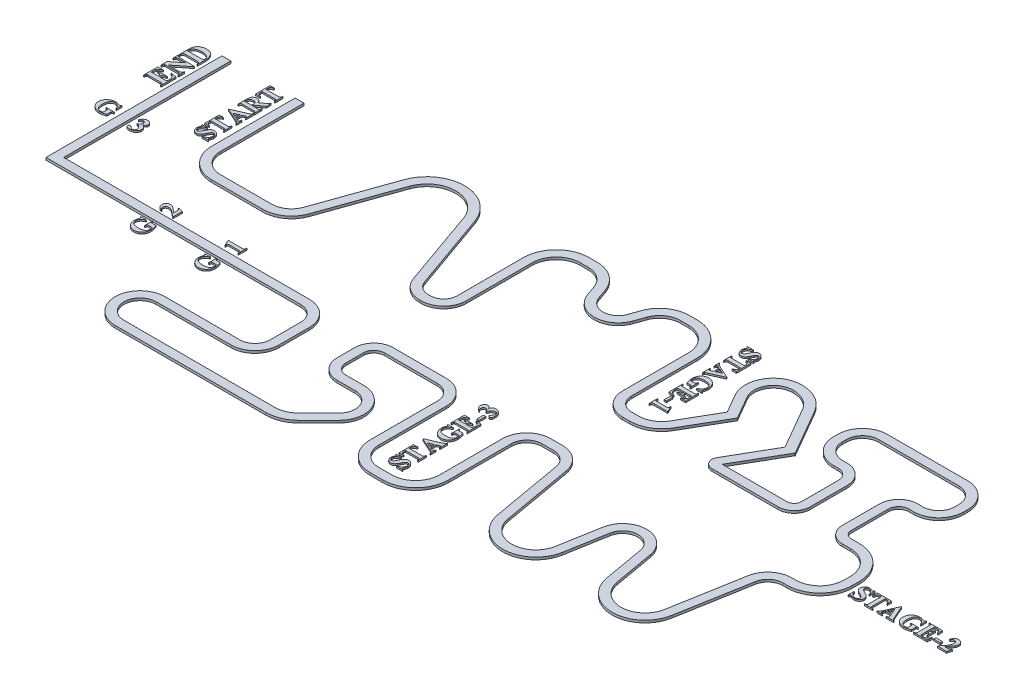
SolidWorks part; units mm, degrees
ref_plane "Front Plane" through (0, 0, 0) normal (0, 0, 1) x (1, 0, 0)
ref_plane "Top Plane" through (0, 0, 0) normal (0, 1, 0) x (1, 0, 0)
ref_plane "Right Plane" through (0, 0, 0) normal (1, 0, 0) x (0, 0, -1)
sketch "Sketch1" plane through (0, 0, 0) normal (0, 1, 0) x (1, 0, 0)
  line L0 (-2000, 850) -> (-2000, 330)
  line L1 (-1820, 150) -> (-1502.2309, 150)
  line L2 (-1332.5468, 269.9393) -> (-1169.6842, 730.0607)
  line L9 (-1000, 1000) -> (-1000, 0) construction
  line L10 (-658.0192, 243.2861) -> (-830.3158, 730.0607)
  line L11 (-52.8541, 763.3772) -> (-30.4035, 699.9494)
  line L14 (-2000, 590) -> (2060.211, 474.7133) construction
  line L30 (1417.787, -380) -> (1417.787, -1000) construction
  line L56 (1565.5082, -503.9528) -> (1609.9593, -756.0472)
  line L58 (1983.3548, -313.9528) -> (1905.4016, -756.0472)
  line L59 (-165.3476, -710.7107) -> (-290.7029, -836.066)
  line L60 (1805.211, 250) -> (1805.211, 480.1871)
  line L62 (-2000, 0) -> (2000, 0) construction
  line L64 (-2000, 1000) -> (2000, 1000) construction
  line L65 (-2000, 1000) -> (-2000, -1000) construction
  line L66 (704.4982, -190) -> (630.3631, -190)
  line L67 (480.3631, -340) -> (480.3631, -730)
  line L68 (330.3631, -880) -> (250.3631, -880)
  line L69 (130.3631, -760) -> (130.3631, -340)
  line L70 (-19.6369, -190) -> (-349.6369, -190)
  line L71 (-469.6369, -310) -> (-469.6369, -420)
  line L72 (-349.6369, -540) -> (-236.0583, -540)
  line L74 (-396.7689, -880) -> (-1334.6369, -880)
  line L75 (-1334.6369, -880) -> (-1334.6369, -680) construction
  line L76 (-1334.6369, -680) -> (-869.6369, -680)
  line L77 (-719.6369, -530) -> (-719.6369, -340)
  line L78 (-869.6369, -190) -> (-2400, -190)
  line L79 (-2000, -1000) -> (2000, -1000) construction
  line L80 (2000, 1000) -> (2000, -1000) construction
  line L81 (-2000, 1000) -> (2000, -1000) construction
  line L82 (-2000, -1000) -> (2000, 1000) construction
  line L83 (-1200, 1000) -> (-1200, -1000) construction
  line L84 (-400, 1000) -> (-400, -1000) construction
  line L85 (400, 1000) -> (400, -1000) construction
  line L86 (1200, 1000) -> (1200, -1000) construction
  line L87 (-526.0426, 150) -> (-515, 150)
  line L88 (-375, 290) -> (-375, 700)
  line L89 (-225, 850) -> (-175.4038, 850)
  line L91 (597, 700) -> (597, 290)
  line L92 (111, 1000) -> (111, 600) construction
  line L93 (737, 150) -> (781.5299, 150)
  line L94 (954.735, 250) -> (1100.211, 501.9718)
  line L95 (1100.211, 501.9718) -> (1017.5256, 645.1871)
  line L96 (1121.4486, 825.1871) -> (1127, 825.1871)
  line L97 (1256.9038, 750.1871) -> (1405.211, 493.3115)
  line L98 (1405.211, 493.3115) -> (1250.3013, 225)
  line L99 (1293.6025, 150) -> (1705.211, 150)
  line L100 (1685.211, 600.1871) -> (1655.211, 600.1871)
  line L101 (1555.211, 700.1871) -> (1555.211, 725.1871)
  line L102 (1655.211, 825.1871) -> (2155.211, 825.1871)
  line L103 (2255.211, 725.1871) -> (2255.211, 700.1871)
  line L104 (2155.211, 600.1871) -> (2125.211, 600.1871)
  line L105 (2005.211, 480.1871) -> (2005.211, 250)
  line L106 (2105.211, 150) -> (2155.211, 150)
  line L107 (2305.211, 0) -> (2305.211, -40)
  line L108 (2155.211, -190) -> (2131.0759, -190)
  line L109 (852.2193, -313.9528) -> (930.1725, -756.0472)
  line L110 (1270.0659, -503.9528) -> (1225.6148, -756.0472)
  line L111 (-1945, 850) -> (-1945, 330)
  line L112 (-1820, 205) -> (-1502.2309, 205)
  line L113 (-1384.3947, 288.2912) -> (-1221.5321, 748.4126)
  line L114 (-606.1712, 261.638) -> (-778.4679, 748.4126)
  line L115 (-526.0426, 205) -> (-515, 205)
  line L116 (-430, 290) -> (-430, 700)
  line L117 (-225, 905) -> (-175.4038, 905)
  line L118 (-1.0061, 781.729) -> (21.4445, 718.3013)
  line L121 (652, 700) -> (652, 290)
  line L122 (737, 205) -> (781.5299, 205)
  line L123 (907.1036, 277.5) -> (1036.7025, 501.9718)
  line L124 (1036.7025, 501.9718) -> (969.8942, 617.6871)
  line L125 (1121.4486, 880.1871) -> (1127, 880.1871)
  line L126 (1304.5352, 777.6871) -> (1468.7195, 493.3115)
  line L127 (1468.7195, 493.3115) -> (1302.2628, 205)
  line L128 (1302.2628, 205) -> (1705.211, 205)
  line L129 (1750.211, 250) -> (1750.211, 480.1871)
  line L130 (1685.211, 545.1871) -> (1655.211, 545.1871)
  line L131 (1500.211, 700.1871) -> (1500.211, 725.1871)
  line L132 (1655.211, 880.1871) -> (2155.211, 880.1871)
  line L133 (2310.211, 725.1871) -> (2310.211, 700.1871)
  line L134 (2155.211, 545.1871) -> (2125.211, 545.1871)
  line L135 (2060.211, 480.1871) -> (2060.211, 250)
  line L136 (2105.211, 205) -> (2155.211, 205)
  line L137 (2360.211, 0) -> (2360.211, -40)
  line L138 (2155.211, -245) -> (2131.0759, -245)
  line L139 (2037.5192, -323.5034) -> (1959.566, -765.5979)
  line L140 (1511.3438, -513.5034) -> (1555.7948, -765.5979)
  line L141 (1324.2303, -513.5034) -> (1279.7793, -765.5979)
  line L142 (798.0549, -323.5034) -> (876.0081, -765.5979)
  line L143 (704.4982, -245) -> (630.3631, -245)
  line L144 (535.3631, -340) -> (535.3631, -730)
  line L145 (330.3631, -935) -> (250.3631, -935)
  line L146 (75.3631, -760) -> (75.3631, -340)
  line L147 (-19.6369, -245) -> (-349.6369, -245)
  line L148 (-414.6369, -310) -> (-414.6369, -420)
  line L149 (-349.6369, -485) -> (-236.0583, -485)
  line L150 (-126.4567, -749.6016) -> (-251.812, -874.9569)
  line L151 (-396.7689, -935) -> (-1334.6369, -935)
  line L152 (-1334.6369, -625) -> (-869.6369, -625)
  line L153 (-774.6369, -530) -> (-774.6369, -340)
  line L154 (-869.6369, -245) -> (-2455, -245)
  line L155 (-2000, 850) -> (-1945, 850)
  line L157 (223.0061, 781.729) -> (200.5555, 718.3013)
  line L158 (274.8541, 763.3772) -> (252.4035, 699.9494)
  line L159 (447, 905) -> (397.4038, 905)
  line L160 (447, 850) -> (397.4038, 850)
  line L161 (652, 686.4096) -> (652, 290) construction
  line L162 (362.0486, 850) -> (492.3602, 850) construction
  line L163 (362.0486, 905) -> (487.6341, 905) construction
  line L164 (252.4035, 699.9494) -> (263.3909, 766.33) construction
  line L165 (199.026, 714.2729) -> (209.1292, 775.3115) construction
  line L166 (-2400, 850) -> (-2400, -190)
  line L167 (-869.6369, -190) -> (-2000, -190) construction
  line L168 (-2455, 850) -> (-2455, -245)
  line L169 (-2455, -190) -> (-2455, -245) construction
  line L170 (-869.6369, -245) -> (-2000, -245) construction
  line L171 (-2455, 850) -> (-2455, -190) construction
  line L172 (-2455, 850) -> (-2400, 850)
  arc A38 (1905.4016, -756.0472) -> (1609.9593, -756.0472) centre (1757.6804, -730) cw
  arc A39 (1565.5082, -503.9528) -> (1270.0659, -503.9528) centre (1417.787, -530) ccw
  arc A45 (-1169.6842, 730.0607) -> (-830.3158, 730.0607) centre (-1000, 670) cw
  arc A48 (-375, 700) -> (-225, 850) centre (-225, 700) cw
  arc A49 (-30.4035, 699.9494) -> (252.4035, 699.9494) centre (111, 750) ccw
  arc A50 (-175.4038, 850) -> (-52.8541, 763.3772) centre (-175.4038, 720) cw
  arc A52 (930.1725, -756.0472) -> (1225.6148, -756.0472) centre (1077.8937, -730) ccw
  arc A53 (781.5299, 150) -> (954.735, 250) centre (781.5299, 350) ccw
  arc A54 (-2000, 330) -> (-1820, 150) centre (-1820, 330) ccw
  arc A55 (-1502.2309, 150) -> (-1332.5468, 269.9393) centre (-1502.2309, 330) ccw
  arc A56 (597, 290) -> (737, 150) centre (737, 290) ccw
  arc A57 (-515, 150) -> (-375, 290) centre (-515, 290) ccw
  arc A58 (-658.0192, 243.2861) -> (-526.0426, 150) centre (-526.0426, 290) ccw
  arc A59 (1017.5256, 645.1871) -> (1121.4486, 825.1871) centre (1121.4486, 705.1871) cw
  arc A60 (1127, 825.1871) -> (1256.9038, 750.1871) centre (1127, 675.1871) cw
  arc A61 (1250.3013, 225) -> (1293.6025, 150) centre (1293.6025, 200) ccw
  arc A62 (2255.211, 700.1871) -> (2155.211, 600.1871) centre (2155.211, 700.1871) cw
  arc A63 (2155.211, 825.1871) -> (2255.211, 725.1871) centre (2155.211, 725.1871) cw
  arc A64 (1555.211, 725.1871) -> (1655.211, 825.1871) centre (1655.211, 725.1871) cw
  arc A65 (1655.211, 600.1871) -> (1555.211, 700.1871) centre (1655.211, 700.1871) cw
  arc A66 (2005.211, 250) -> (2105.211, 150) centre (2105.211, 250) ccw
  arc A67 (1705.211, 150) -> (1805.211, 250) centre (1705.211, 250) ccw
  arc A68 (480.3631, -730) -> (330.3631, -880) centre (330.3631, -730) cw
  arc A69 (630.3631, -190) -> (480.3631, -340) centre (630.3631, -340) ccw
  arc A70 (852.2193, -313.9528) -> (704.4982, -190) centre (704.4982, -340) ccw
  arc A71 (2131.0759, -190) -> (1983.3548, -313.9528) centre (2131.0759, -340) ccw
  arc A72 (2305.211, -40) -> (2155.211, -190) centre (2155.211, -40) cw
  arc A73 (2155.211, 150) -> (2305.211, 0) centre (2155.211, 0) cw
  arc A74 (250.3631, -880) -> (130.3631, -760) centre (250.3631, -760) cw
  arc A75 (130.3631, -340) -> (-19.6369, -190) centre (-19.6369, -340) ccw
  arc A76 (-469.6369, -420) -> (-349.6369, -540) centre (-349.6369, -420) ccw
  arc A77 (-349.6369, -190) -> (-469.6369, -310) centre (-349.6369, -310) ccw
  arc A78 (-236.0583, -540) -> (-165.3476, -710.7107) centre (-236.0583, -640) cw
  arc A79 (-719.6369, -340) -> (-869.6369, -190) centre (-869.6369, -340) ccw
  arc A80 (-869.6369, -680) -> (-719.6369, -530) centre (-869.6369, -530) ccw
  arc A81 (-290.7029, -836.066) -> (-396.7689, -880) centre (-396.7689, -730) cw
  arc A82 (-1334.6369, -880) -> (-1334.6369, -680) centre (-1334.6369, -780) cw
  arc A83 (2125.211, 600.1871) -> (2005.211, 480.1871) centre (2125.211, 480.1871) ccw
  arc A84 (1805.211, 480.1871) -> (1685.211, 600.1871) centre (1685.211, 480.1871) ccw
  arc A85 (-1945, 330) -> (-1820, 205) centre (-1820, 330) ccw
  arc A86 (-1502.2309, 205) -> (-1384.3947, 288.2912) centre (-1502.2309, 330) ccw
  arc A87 (-1221.5321, 748.4126) -> (-778.4679, 748.4126) centre (-1000, 670) cw
  arc A88 (-606.1712, 261.638) -> (-526.0426, 205) centre (-526.0426, 290) ccw
  arc A89 (-515, 205) -> (-430, 290) centre (-515, 290) ccw
  arc A90 (-430, 700) -> (-225, 905) centre (-225, 700) cw
  arc A91 (-175.4038, 905) -> (-1.0061, 781.729) centre (-175.4038, 720) cw
  arc A92 (21.4445, 718.3013) -> (200.5555, 718.3013) centre (111, 750) ccw
  arc A95 (652, 290) -> (737, 205) centre (737, 290) ccw
  arc A96 (781.5299, 205) -> (907.1036, 277.5) centre (781.5299, 350) ccw
  arc A97 (969.8942, 617.6871) -> (1121.4486, 880.1871) centre (1121.4486, 705.1871) cw
  arc A98 (1127, 880.1871) -> (1304.5352, 777.6871) centre (1127, 675.1871) cw
  arc A99 (1302.2628, 205) -> (1302.2628, 205) centre (1302.2628, 205) ccw
  arc A100 (1705.211, 205) -> (1750.211, 250) centre (1705.211, 250) ccw
  arc A101 (1750.211, 480.1871) -> (1685.211, 545.1871) centre (1685.211, 480.1871) ccw
  arc A102 (1655.211, 545.1871) -> (1500.211, 700.1871) centre (1655.211, 700.1871) cw
  arc A103 (1500.211, 725.1871) -> (1655.211, 880.1871) centre (1655.211, 725.1871) cw
  arc A104 (2155.211, 880.1871) -> (2310.211, 725.1871) centre (2155.211, 725.1871) cw
  arc A105 (2310.211, 700.1871) -> (2155.211, 545.1871) centre (2155.211, 700.1871) cw
  arc A106 (2125.211, 545.1871) -> (2060.211, 480.1871) centre (2125.211, 480.1871) ccw
  arc A107 (2060.211, 250) -> (2105.211, 205) centre (2105.211, 250) ccw
  arc A108 (2155.211, 205) -> (2360.211, 0) centre (2155.211, 0) cw
  arc A109 (2360.211, -40) -> (2155.211, -245) centre (2155.211, -40) cw
  arc A110 (2131.0759, -245) -> (2037.5192, -323.5034) centre (2131.0759, -340) ccw
  arc A111 (1959.566, -765.5979) -> (1555.7948, -765.5979) centre (1757.6804, -730) cw
  arc A112 (1511.3438, -513.5034) -> (1324.2303, -513.5034) centre (1417.787, -530) ccw
  arc A113 (876.0081, -765.5979) -> (1279.7793, -765.5979) centre (1077.8937, -730) ccw
  arc A114 (798.0549, -323.5034) -> (704.4982, -245) centre (704.4982, -340) ccw
  arc A115 (630.3631, -245) -> (535.3631, -340) centre (630.3631, -340) ccw
  arc A116 (535.3631, -730) -> (330.3631, -935) centre (330.3631, -730) cw
  arc A117 (250.3631, -935) -> (75.3631, -760) centre (250.3631, -760) cw
  arc A118 (75.3631, -340) -> (-19.6369, -245) centre (-19.6369, -340) ccw
  arc A119 (-349.6369, -245) -> (-414.6369, -310) centre (-349.6369, -310) ccw
  arc A120 (-414.6369, -420) -> (-349.6369, -485) centre (-349.6369, -420) ccw
  arc A121 (-236.0583, -485) -> (-126.4567, -749.6016) centre (-236.0583, -640) cw
  arc A122 (-251.812, -874.9569) -> (-396.7689, -935) centre (-396.7689, -730) cw
  arc A123 (-1334.6369, -935) -> (-1334.6369, -625) centre (-1334.6369, -780) cw
  arc A124 (-869.6369, -625) -> (-774.6369, -530) centre (-869.6369, -530) ccw
  arc A125 (-774.6369, -340) -> (-869.6369, -245) centre (-869.6369, -340) ccw
  arc A126 (397.4038, 850) -> (274.8541, 763.3772) centre (397.4038, 720) ccw
  arc A127 (397.4038, 905) -> (223.0061, 781.729) centre (397.4038, 720) ccw
  arc A128 (597, 700) -> (447, 850) centre (447, 700) ccw
  arc A129 (652, 700) -> (447, 905) centre (447, 700) ccw
  arc A130 (597, 700) -> (492.3602, 850) centre (511.4903, 751.8469) ccw construction
  arc A131 (652, 686.4096) -> (487.6341, 905) centre (511.4903, 751.8469) ccw construction
  arc A132 (362.0486, 850) -> (263.3909, 766.33) centre (362.0486, 750) ccw construction
  arc A133 (362.0486, 905) -> (209.1292, 775.3115) centre (362.0486, 750) ccw construction
  arc A134 (21.4445, 718.3013) -> (199.026, 714.2729) centre (111, 750) ccw construction
  point P14 (-375, 850)
  point P23 (-83.5147, 850)
  point P52 (897, 150)
  point P54 (4220.4062, -343.1918)
  point P58 (-2000, 150)
  point P61 (-1375, 150)
  point P64 (597, 150)
  point P67 (-375, 150)
  point P71 (-625, 150)
  point P73 (1757.6804, -880)
  point P76 (0, 0)
  point P87 (-1000, 850)
  point P95 (913.6025, 825.1871)
  point P97 (1077.8937, -880)
  point P99 (1213.6025, 825.1871)
  point P106 (2255.211, 825.1871)
  point P109 (1555.211, 825.1871)
  point P114 (2005.211, 150)
  point P117 (1805.211, 150)
  point P126 (830.3631, -190)
  point P129 (2005.211, -190)
  point P132 (2305.211, -190)
  point P135 (2305.211, 150)
  point P148 (130.3631, -190)
  point P151 (2432.0949, -360.4159)
  point P152 (-469.6369, -540)
  point P156 (480.3631, -190)
  point P157 (-469.6369, -190)
  point P161 (5.3631, -540)
  point P171 (-334.6369, -880)
  point P172 (4140.4062, -123.1918)
  point P173 (3698.8517, 0)
  point P174 (3778.8517, -80)
  point P176 (4220.4062, -123.1918)
  point P181 (1805.211, 600.1871)
  dimension "D4" = 2000
  dimension "D7" = 625
  dimension "D8" = 225
  dimension "D9" = 180
  dimension "D5" = 700
  dimension "D12" = 800
  dimension "D13" = 4
  dimension "D21" = 130
  dimension "D22" = 150
  dimension "D40" = 730
  dimension "D41" = 500
  dimension "D42" = 350
  dimension "D43" = 350
  dimension "D44" = 600
  dimension "D45" = 475
  dimension "D46" = 45
  dimension "D47" = 250
  dimension "D51" = 180
  dimension "D52" = 140
  dimension "D54" = 150
  dimension "D56" = 100
  dimension "D59" = 120
  dimension "D61" = 120
  dimension "D62" = 100
  dimension "D35" = 100
  dimension "D29" = 120
  dimension "D32" = 350
  dimension "D33" = 200
  dimension "D34" = 150
  dimension "D37" = 150
  dimension "D48" = 1000
  dimension "D49" = 200
  dimension "D53" = 120
  dimension "D55" = 50
  dimension "D57" = 100
  dimension "D58" = 150
  dimension "D30" = 150
  dimension "D11" = 200
  dimension "D14" = 250
  dimension "D15" = 800
  dimension "D17" = 475
  dimension "D6" = 180
  dimension "D19" = 150
  dimension "D20" = 400
  dimension "D25" = 344.5965
  dimension "D38" = 150
  dimension "D39" = 300
  dimension "D50" = 200
  dimension "D60" = 150
  dimension "D63" = 150
  dimension "D64" = 305
  dimension "D65" = 120
  dimension "D10" = 486
  dimension "D2" = 4000
  dimension "D16" = 150
  dimension "D18" = 1610.1871
  dimension "D23" = 250
  dimension "D24" = 55
  dimension "D26" = 300
  dimension "D27" = 300
  dimension "D31" = 700
  dimension "D36" = 340
  dimension "D28" = 120
  dimension "D66" = 55
  dimension "D67" = 4815.211
  dimension "D68" = 1095
extrude "Boss-Extrude1" add sketch "Sketch1" along normal blind 15
sketch "Sketch2" plane through (0, 0, 0) normal (0, 1, 0) x (1, 0, 0)
  line L0 (-2050, 850) -> (-2050, 350) construction
  line L1 (-2490, 850) -> (-2490, 350) construction
  line L2 (742, 190) -> (742, 1040) construction
  line L4 (492, 1040) -> (992, 1040) construction
  line L5 (2351.2339, -100) -> (3051.2339, -100) construction
  line L6 (-2000, 0) -> (2000, 0) construction
  line L7 (330.3631, -880) -> (330.3631, -130) construction
  line L9 (-1344.6369, 0) -> (-1344.6369, -400) construction
  line L11 (-1744.6369, 0) -> (-1744.6369, -400) construction
  line L12 (-2655, 175) -> (-2255, 175) construction
  line L13 (-2455, 850) -> (-2455, -245) construction
  line L14 (652, 290) -> (652, 700) construction
  arc A0 (2155.211, -245) -> (2360.211, -40) centre (2155.211, -40) ccw construction
  text T0 "START" font "Times New Roman" height 100
  text T1 "END" font "Times New Roman" height 110
  text T2 "STAGE-1" font "Times New Roman" height 100
  text T3 "STAGE-3" font "Times New Roman" height 100
  text T4 "STAGE-2" font "Times New Roman" height 100
  text T5 "G 1 " font "Times New Roman" height 100
  text T6 "G 2 " font "Times New Roman" height 100
  text T7 "G  3" font "Times New Roman" height 100
  point P17 (742, 1040)
  point P32 (-1344.6369, -200)
  point P35 (-2455, 175)
  dimension "D1" = 50
  dimension "D2" = 500
  dimension "D4" = 850
  dimension "D5" = 500
  dimension "D6" = 750
  dimension "D7" = 145
  dimension "D8" = 700
  dimension "D9" = 200
  dimension "D10" = 475
  dimension "D11" = 400
  dimension "D12" = 400
  dimension "D13" = 420
  dimension "D14" = 90
  dimension "D3" = 440
extrude "Boss-Extrude2" add sketch "Sketch2" along normal blind 10 separate body
sketch "Sketch3" plane through (0, 0, 0) normal (0, 1, 0) x (1, 0, 0)
  line L1 (-2855, -1277) -> (3345, -1277) construction
  line L2 (-2855, -1277) -> (-2855, 1223) construction
  line L3 (-2855, 1223) -> (3345, 1223) construction
  line L4 (3345, -1277) -> (3345, 1223) construction
  line L5 (-2455, 850) -> (-2455, -245) construction
  line L6 (-1334.6369, -935) -> (-396.7689, -935) construction
  point P0 (0, 0)
  dimension "D1" = 6200
  dimension "D2" = 2500
  dimension "D3" = 400
  dimension "D4" = 342
